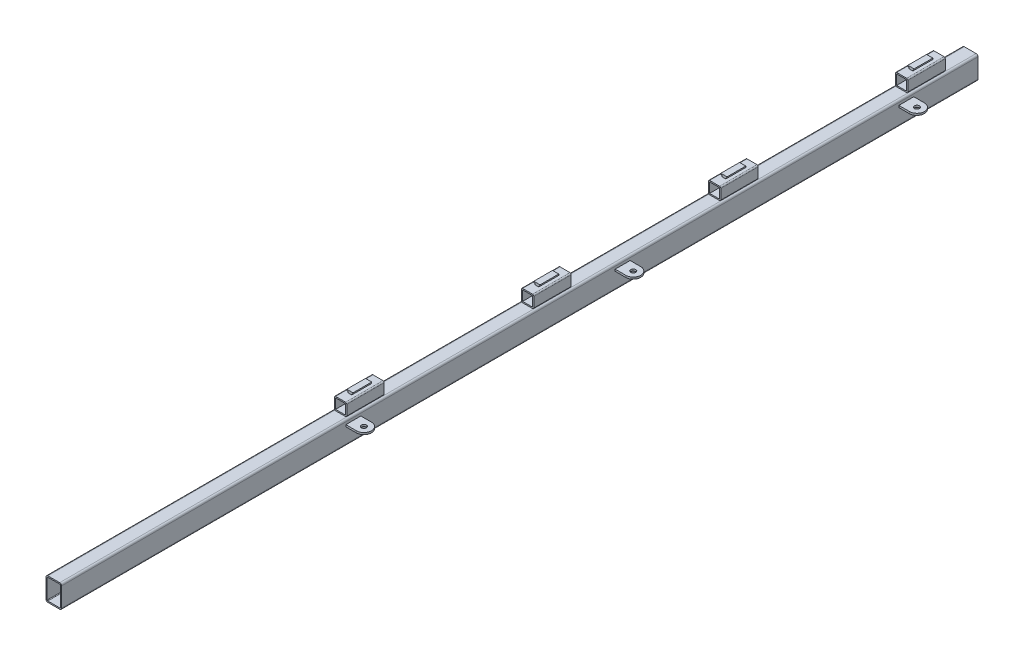
SolidWorks part; units mm, degrees
material "Alloy Steel"
ref_plane "Front" through (0, 0, 0) normal (0, 0, 1) x (1, 0, 0)
ref_plane "Top" through (0, 0, 0) normal (0, 1, 0) x (1, 0, 0)
ref_plane "Right" through (0, 0, 0) normal (1, 0, 0) x (0, 0, -1)
sketch "Sketch1" plane through (0, 0, 0) normal (0, 0, 1) x (1, 0, 0)
  line L0 (0, 40.8909) -> (0, -24.1212) construction
  line L1 (-9.5, 37) -> (9.5, 37)
  line L2 (-12.5, 34) -> (-12.5, 3)
  line L3 (-9.5, 0) -> (9.5, 0)
  line L4 (12.5, 34) -> (12.5, 3)
  arc A0 (-12.5, 3) -> (-9.5, 0) centre (-9.5, 3) ccw
  arc A1 (9.5, 0) -> (12.5, 3) centre (9.5, 3) ccw
  arc A2 (9.5, 37) -> (12.5, 34) centre (9.5, 34) cw
  arc A3 (-9.5, 37) -> (-12.5, 34) centre (-9.5, 34) ccw
  point P9 (-12.5, 0)
  point P12 (12.5, 0)
  point P15 (12.5, 37)
  dimension "D3" = 3
  dimension "D1" = 37
  dimension "D2" = 25
extrude "Extrude-Thin1" add sketch "Sketch1" along normal blind 1470 thin contours L1 A2 L4 A1 L3 A0 L2 A3 thin type one direction reverse wall 2
ref_plane "Plane1" through (0, 27, 0) normal (0, 1, 0) x (1, 0, 0)
sketch "Sketch2" plane through (0, 27, 0) normal (0, 1, 0) x (1, 0, 0)
  line L0 (29.5, -103) -> (12.5, -103)
  line L1 (12.5, -1470) -> (12.5, 0) construction
  line L2 (12.5, -103) -> (12.5, -127)
  line L3 (12.5, -127) -> (29.5, -127)
  line L4 (-9.5, 0) -> (9.5, 0) construction
  line L5 (29.5, -558) -> (12.5, -558)
  line L6 (12.5, -558) -> (12.5, -582)
  line L7 (12.5, -582) -> (29.5, -582)
  line L8 (29.5, -990) -> (12.5, -990)
  line L9 (12.5, -990) -> (12.5, -1014)
  line L10 (12.5, -1014) -> (29.5, -1014)
  arc A0 (29.5, -103) -> (29.5, -127) centre (29.5, -115) cw
  circle A1 centre (29.5, -115) radius 4
  arc A2 (29.5, -558) -> (29.5, -582) centre (29.5, -570) cw
  circle A3 centre (29.5, -570) radius 4
  arc A4 (29.5, -990) -> (29.5, -1014) centre (29.5, -1002) cw
  circle A5 centre (29.5, -1002) radius 4
  dimension "D1" = 8
  dimension "D2" = 12
  dimension "D5" = 8
  dimension "D6" = 12
  dimension "D9" = 8
  dimension "D10" = 12
  dimension "D3" = 17
  dimension "D4" = 115
  dimension "D8" = 570
  dimension "D12" = 1002
extrude "Boss-Extrude1" add sketch "Sketch2" along normal blind 3
ref_plane "Plane2" through (0, 0, 50) normal (0, 0, -1) x (-1, 0, 0)
sketch "Sketch3" plane through (0, 0, 50) normal (0, 0, -1) x (-1, 0, 0)
  line L0 (0, 62.5541) -> (0, 30.9171) construction
  line L1 (-8, 57) -> (8, 57)
  line L2 (-10, 55) -> (-10, 39)
  line L3 (-8, 37) -> (8, 37)
  line L4 (10, 55) -> (10, 39)
  line L5 (-10.5, 34) -> (-10.5, 3) construction
  line L6 (10.5, 34) -> (10.5, 3) construction
  line L7 (9.5, 37) -> (-9.5, 37) construction
  arc A0 (8, 37) -> (10, 39) centre (8, 39) ccw
  arc A1 (-10, 39) -> (-8, 37) centre (-8, 39) ccw
  arc A2 (-8, 57) -> (-10, 55) centre (-8, 55) ccw
  arc A3 (8, 57) -> (10, 55) centre (8, 55) cw
  point P14 (10, 37)
  point P21 (10, 57)
  dimension "D2" = 2
  dimension "D1" = 20
extrude "Extrude-Thin2" add sketch "Sketch3" against normal blind 60 thin contours L1 A3 L4 A0 L3 A1 L2 A2 thin type one direction reverse wall 2
ref_plane "Plane3" through (0, 0, 80) normal (0, 0, 1) x (1, 0, 0)
sketch "Sketch4" plane through (0, 0, 80) normal (0, 0, 1) x (1, 0, 0)
  line L0 (-3, 57) -> (-3, 59)
  line L2 (-3, 59) -> (-5, 59)
  line L3 (-5, 59) -> (-5, 61)
  line L4 (-5, 61) -> (5, 61)
  line L5 (5, 61) -> (5, 59)
  line L6 (5, 59) -> (3, 59)
  line L7 (3, 59) -> (3, 57)
  line L8 (3, 57) -> (-3, 57)
  line L9 (0, 63.1918) -> (0, 54.2911) construction
  line L10 (8, 57) -> (-8, 57) construction
  dimension "D1" = 2
  dimension "D2" = 10
  dimension "D3" = 6
  dimension "D4" = 2
extrude "Boss-Extrude2" add sketch "Sketch4" along normal mid plane 30
pattern_linear "LPattern1" count 4 spacing 300 along (0, 0, 1) of "Extrude-Thin2", "Boss-Extrude2"
